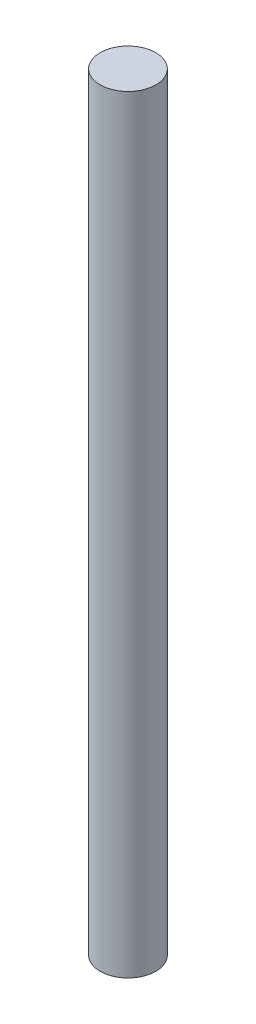
SolidWorks part; units mm, degrees
ref_plane "Front Plane" through (0, 0, 0) normal (0, 0, 1) x (1, 0, 0)
ref_plane "Top Plane" through (0, 0, 0) normal (0, 1, 0) x (1, 0, 0)
ref_plane "Right Plane" through (0, 0, 0) normal (1, 0, 0) x (0, 0, -1)
sketch "Sketch1" plane through (0, 0, 0) normal (0, 1, 0) x (1, 0, 0)
  circle A0 centre (0, 0) radius 12.446
  dimension "D1" = 24.892
extrude "Boss-Extrude1" add sketch "Sketch1" along normal blind 342.9
ref_axis "center axis" through (0, 342.9, 0) along (0, -1, 0)
